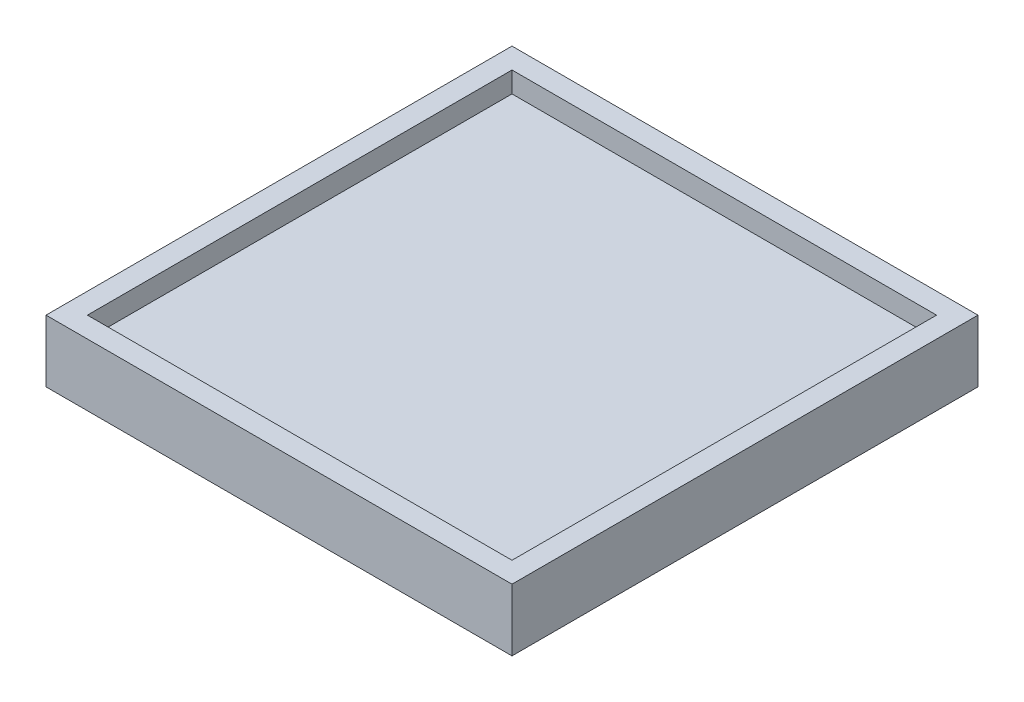
SolidWorks part; units mm, degrees
ref_plane "Front Plane" through (0, 0, 0) normal (0, 0, 1) x (1, 0, 0)
ref_plane "Top Plane" through (0, 0, 0) normal (0, 1, 0) x (1, 0, 0)
ref_plane "Right Plane" through (0, 0, 0) normal (1, 0, 0) x (0, 0, -1)
sketch "Sketch1" plane through (0, 0, 0) normal (0, 1, 0) x (1, 0, 0)
  line L1 (92, 100) -> (-133, 100)
  line L2 (92, 100) -> (92, -125)
  line L3 (92, -125) -> (-133, -125)
  line L4 (-133, 100) -> (-133, -125)
  line L7 (82, 90) -> (-123, 90)
  line L8 (82, 90) -> (82, -115)
  line L9 (82, -115) -> (-123, -115)
  line L10 (-123, 90) -> (-123, -115)
  point P0 (0, 0)
  point P6 (0, 0)
  dimension "D1" = 225
  dimension "D2" = 225
  dimension "D3" = 10
  dimension "D4" = 10
  dimension "D5" = 10
  dimension "D6" = 205
extrude "Walls" add sketch "Sketch1" along normal blind 30 contours L1 L4 L3 L2 L10 L7 L8 L9 region at (88.818, 0, 12.5)
extrude "Boss-Extrude2" add sketch "Sketch1<5>" along normal blind 20 contours L7 L10 L9 L8 region at (-20.5, 0, 12.5)
sketch "Sketch1<5>" plane through (0, 0, 0) normal (0, 1, 0) x (1, 0, 0) same geometry as "Sketch1"
equation "\"hight\"=110"
equation "\"D5@Sketch1\"=\"D4@Sketch1\""
equation "\"D3@Sketch1\"=\"D5@Sketch1\""
